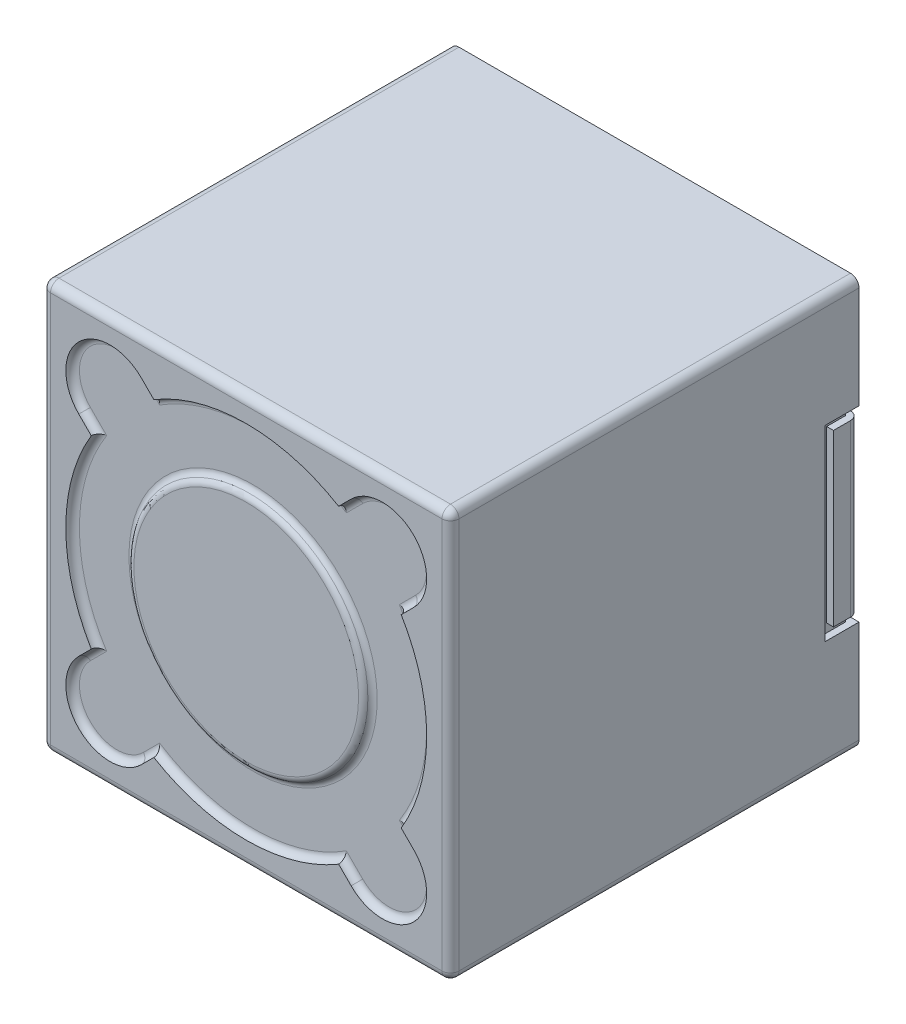
SolidWorks part; units mm, degrees
ref_plane "Front Plane" through (0, 0, 0) normal (0, 0, 1) x (1, 0, 0)
ref_plane "Top Plane" through (0, 0, 0) normal (0, 1, 0) x (1, 0, 0)
ref_plane "Right Plane" through (0, 0, 0) normal (1, 0, 0) x (0, 0, -1)
sketch "Sketch2" plane through (0, 0, 0) normal (0, 0, 1) x (1, 0, 0)
  line L1 (-6, 6) -> (6, 6)
  line L2 (-6, 6) -> (-6, -6)
  line L3 (-6, -6) -> (6, -6)
  line L4 (6, 6) -> (6, -6)
  point P4 (6, 0)
  point P6 (0, 6)
  dimension "D1" = 12
  dimension "D2" = 12
extrude "Boss-Extrude1" add sketch "Sketch2" along normal blind 12
sketch "Sketch3" plane through (0, 0, 0) normal (0, 0, -1) x (-1, 0, 0)
  line L0 (-6, -6) -> (-6, 6) construction
  line L1 (-6, -2.75) -> (-3.45, -2.75)
  line L2 (-6, -2.75) -> (-6, 2.75)
  line L3 (-6, 2.75) -> (-3.45, 2.75)
  line L4 (-3.45, -2.75) -> (-3.45, 2.75)
  line L5 (6, 6) -> (6, -6) construction
  line L6 (3.45, 2.75) -> (6, 2.75)
  line L7 (3.45, 2.75) -> (3.45, -2.75)
  line L8 (3.45, -2.75) -> (6, -2.75)
  line L9 (6, 2.75) -> (6, -2.75)
  point P12 (-6, 0)
  point P13 (-6, 0)
  dimension "D1" = 5.5
  dimension "D2" = 2.55
extrude "Cut-Extrude1" cut sketch "Sketch3" against normal blind 0.2
sketch "Sketch4" plane through (6, 0, 0) normal (1, 0, 0) x (0, 0, -1)
  line L0 (0, 2.75) -> (0, 6) construction
  line L1 (-0.2, -2.75) -> (-1, -2.75)
  line L2 (-0.2, -2.75) -> (-0.2, 2.75)
  line L3 (-0.2, 2.75) -> (-1, 2.75)
  line L4 (-1, -2.75) -> (-1, 2.75)
  point P7 (0, 0)
  dimension "D1" = 1
extrude "Cut-Extrude2" cut sketch "Sketch4" against normal blind 0.2
mirror "Mirror1" about plane through (0, 0, 0) normal (1, 0, 0) of "Cut-Extrude2"
fillet "Fillet1" radius 0.25 8 edges at (0, 6, 12) (6, 0, 12) (0, -6, 12) (-6, 0, 12) (6, -6, 6) (-6, -6, 6) (-6, 6, 6) (6, 6, 6)
sketch "Sketch5" plane through (0, 0, 0) normal (0, 0, -1) x (-1, 0, 0)
  line L0 (-6, 2.75) -> (-6, -2.75) construction
  line L1 (-3.7, 2.5) -> (-6, 2.5)
  line L2 (-3.7, 2.5) -> (-3.7, -2.5)
  line L3 (-3.7, -2.5) -> (-6, -2.5)
  line L4 (-6, 2.5) -> (-6, -2.5)
  line L5 (3.7, 2.5) -> (6, 2.5)
  line L6 (3.7, 2.5) -> (3.7, -2.5)
  line L7 (3.7, -2.5) -> (6, -2.5)
  line L8 (6, 2.5) -> (6, -2.5)
  line L9 (-3.45, 2.75) -> (-6, 2.75) construction
  line L11 (-3.45, -2.75) -> (-3.45, 2.75) construction
  line L12 (-5.8, -2.75) -> (-3.45, -2.75) construction
  line L13 (6, 2.75) -> (6, -2.75) construction
  dimension "D1" = 0.25
  dimension "D2" = 0.25
  dimension "D3" = 0.25
extrude "Boss-Extrude2" add sketch "Sketch5" against normal blind 0.75
fillet "Fillet2" radius 0.25 2 edges at (-6, 0, 0) (6, 0, 0)
sketch "Sketch6" plane through (0, 0, 12) normal (0, 0, 1) x (1, 0, 0)
  line L0 (6, 5.75) -> (6, -5.75) construction
  line L1 (5.75, -6) -> (-5.75, -6) construction
  line L2 (-6, -5.75) -> (-6, 5.75) construction
  line L3 (-5.75, 6) -> (5.75, 6) construction
  line L5 (3.0808, -4.9192) -> (2.7139, -4.5524)
  line L6 (4.9192, -3.0808) -> (4.5524, -2.7139)
  line L7 (4.9192, 3.0808) -> (4.5524, 2.7139)
  line L8 (3.0808, 4.9192) -> (2.7139, 4.5524)
  line L11 (-2.7139, 4.5524) -> (-3.0808, 4.9192)
  line L12 (-4.5524, 2.7139) -> (-4.9192, 3.0808)
  line L13 (-4.5524, -2.7139) -> (-4.9192, -3.0808)
  line L14 (-2.7139, -4.5524) -> (-3.0808, -4.9192)
  circle A0 centre (0, 0) radius 3.5
  arc A1 (4.5524, -2.7139) -> (4.5524, 2.7139) centre (0, 0) ccw
  arc A2 (-4.9192, -3.0808) -> (-3.0808, -4.9192) centre (-4, -4) ccw
  arc A3 (3.0808, -4.9192) -> (4.9192, -3.0808) centre (4, -4) ccw
  arc A4 (4.9192, 3.0808) -> (3.0808, 4.9192) centre (4, 4) ccw
  arc A5 (-3.0808, 4.9192) -> (-4.9192, 3.0808) centre (-4, 4) ccw
  arc A6 (-2.7139, -4.5524) -> (2.7139, -4.5524) centre (0, 0) ccw
  arc A7 (-4.5524, 2.7139) -> (-4.5524, -2.7139) centre (0, 0) ccw
  arc A8 (2.7139, 4.5524) -> (-2.7139, 4.5524) centre (0, 0) ccw
  point P31 (3.0808, 4.9192)
  point P34 (3.0808, 4.9192)
  dimension "D2" = 7
  dimension "D3" = 10.6
  dimension "D4" = 2.6
  dimension "D1" = 2
  dimension "D5" = 2
  dimension "D6" = 2
  dimension "D7" = 2
extrude "Cut-Extrude3" cut sketch "Sketch6" against normal blind 0.2
fillet "Fillet3" radius 0.2 1 edges at (3.5, 0, 12)
fillet "Fillet4" radius 0.2 17 edges at (2.8974, -4.7358, 11.8) (0, -5.3, 11.8) (-2.8974, -4.7358, 11.8) (-4.9192, -4.9192, 11.8) (-4.7358, -2.8974, 11.8) (-5.3, 0, 11.8) (-4.7358, 2.8974, 11.8) (-4.9192, 4.9192, 11.8) (-2.8974, 4.7358, 11.8) (0, 5.3, 11.8) (2.8974, 4.7358, 11.8) (4.9192, 4.9192, 11.8) (4.7358, 2.8974, 11.8) (5.3, 0, 11.8) (4.7358, -2.8974, 11.8) (4.9192, -4.9192, 11.8) (3.5, 0, 11.8)
